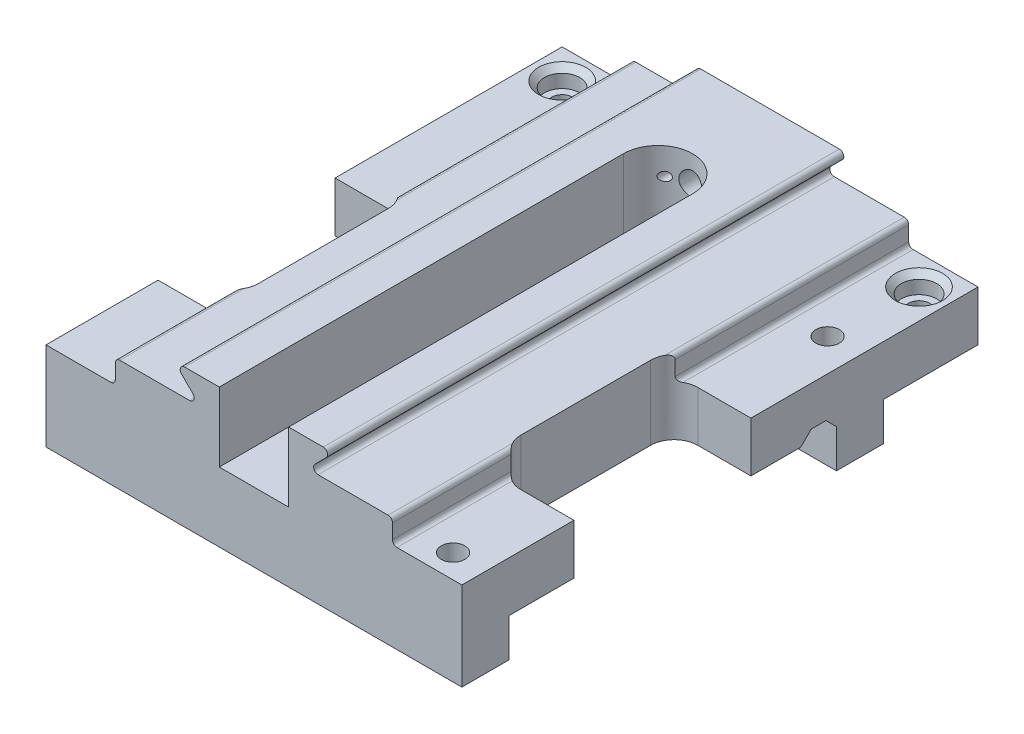
SolidWorks part; units mm, degrees
material "AISI 1020"
ref_plane "Front Plane" through (0, 0, 0) normal (0, 0, 1) x (1, 0, 0)
ref_plane "Top Plane" through (0, 0, 0) normal (0, 1, 0) x (1, 0, 0)
ref_plane "Right Plane" through (0, 0, 0) normal (1, 0, 0) x (0, 0, -1)
sketch "Sketch1" plane through (0, 0, 0) normal (0, 0, 1) x (1, 0, 0)
  line L0 (-70.5, -23.5) -> (-70.5, 23.5) construction
  line L1 (70.5, -23.5) -> (-70.5, -23.5) construction
  line L2 (70.5, -23.5) -> (70.5, 23.5) construction
  line L3 (70.5, 23.5) -> (-70.5, 23.5) construction
  line L4 (-70.5, -23.5) -> (-70.5, 23.5) construction
  line L5 (70.5, -23.5) -> (-70.5, 23.5) construction
  line L6 (70.5, 23.5) -> (-70.5, -23.5) construction
  line L7 (24.5607, 20.9393) -> (20.682, 17.0607)
  line L8 (21.7426, 14.5) -> (45.5, 14.5)
  line L9 (47, 13) -> (47, 8)
  line L10 (48.5, 6.5) -> (70.5, 6.5)
  line L11 (70.5, 6.5) -> (70.5, -23.5)
  line L12 (70.5, -23.5) -> (-70.5, -23.5)
  line L13 (0, -23.5) -> (0, 23.5) construction
  line L14 (-23.5, 23.5) -> (23.5, 23.5)
  line L15 (-70.5, 6.5) -> (-70.5, -23.5)
  line L16 (-48.5, 6.5) -> (-70.5, 6.5)
  line L17 (-47, 13) -> (-47, 8)
  line L18 (-21.7426, 14.5) -> (-45.5, 14.5)
  line L19 (-24.5607, 20.9393) -> (-20.682, 17.0607)
  line L20 (-7, 14.5) -> (7, 14.5) construction
  arc A0 (23.5, 23.5) -> (24.5607, 20.9393) centre (23.5, 22) cw
  arc A1 (20.682, 17.0607) -> (21.7426, 14.5) centre (21.7426, 16) ccw
  arc A2 (45.5, 14.5) -> (47, 13) centre (45.5, 13) cw
  arc A3 (47, 8) -> (48.5, 6.5) centre (48.5, 8) ccw
  arc A4 (-47, 8) -> (-48.5, 6.5) centre (-48.5, 8) cw
  arc A5 (-45.5, 14.5) -> (-47, 13) centre (-45.5, 13) ccw
  arc A6 (-20.682, 17.0607) -> (-21.7426, 14.5) centre (-21.7426, 16) cw
  arc A7 (-23.5, 23.5) -> (-24.5607, 20.9393) centre (-23.5, 22) ccw
  circle A8 centre (0, 14.5) radius 4
  circle A9 centre (7, 14.5) radius 1.5
  circle A10 centre (-7, 14.5) radius 1.5
  point P0 (0, 0)
  point P9 (0, 23.5)
  point P44 (0, 14.5)
  dimension "D10" = 8
  dimension "D12" = 3
  dimension "D3" = 9
  dimension "D4" = 45
  dimension "D7" = 141
  dimension "D8" = 94
  dimension "D9" = 9
  dimension "D11" = 14
  dimension "D5" = 30
extrude "Boss-Extrude1" add sketch "Sketch1" against normal blind 175
sketch "Sketch2" plane through (0, 0, 0) normal (0, 1, 0) x (1, 0, 0)
  line L0 (0, 0) -> (0, 137) construction
  line L1 (-11.75, 0) -> (-11.75, 137)
  line L2 (11.75, 0) -> (11.75, 137)
  line L3 (23.5, 175) -> (-23.5, 175) construction
  line L4 (-70.5, 175) -> (-70.5, 0) construction
  line L5 (-48.5, 175) -> (-70.5, 175) construction
  line L6 (0, 175) -> (0, 0) construction
  arc A0 (-11.75, 0) -> (11.75, 0) centre (0, 0) ccw
  arc A1 (11.75, 137) -> (-11.75, 137) centre (0, 137) ccw
  circle A2 centre (-60.5, 165) radius 6
  circle A3 centre (60.5, 165) radius 6
  point P3 (0, 68.5)
  dimension "D5" = 12
  dimension "D1" = 23.5
  dimension "D2" = 38
  dimension "D3" = 10
  dimension "D4" = 10
extrude "Cut-Extrude1" cut sketch "Sketch2" along normal through all
sketch "Sketch3" plane through (0, 0, 0) normal (0, 1, 0) x (1, 0, 0)
  line L0 (-70.5, 98) -> (-52.5, 98)
  line L1 (-70.5, 175) -> (-70.5, 0) construction
  line L2 (-44.5, 90) -> (-44.5, 46)
  line L3 (-52.5, 38) -> (-70.5, 38)
  line L4 (-70.5, 38) -> (-70.5, 98)
  line L5 (-48.5, 0) -> (-70.5, 0) construction
  line L7 (0, 0) -> (0, 175) construction
  line L8 (23.5, 175) -> (-23.5, 175) construction
  line L9 (11.75, 0) -> (-11.75, 0) construction
  line L10 (70.5, 38) -> (70.5, 98)
  line L11 (52.5, 38) -> (70.5, 38)
  line L12 (44.5, 90) -> (44.5, 46)
  line L13 (70.5, 98) -> (52.5, 98)
  circle A0 centre (-60.5, 165) radius 3.5
  arc A2 (-52.5, 98) -> (-44.5, 90) centre (-52.5, 90) cw
  arc A3 (-44.5, 46) -> (-52.5, 38) centre (-52.5, 46) cw
  circle A4 centre (0, 24) radius 5
  arc A5 (44.5, 46) -> (52.5, 38) centre (52.5, 46) ccw
  arc A6 (52.5, 98) -> (44.5, 90) centre (52.5, 90) ccw
  circle A7 centre (60.5, 165) radius 3.5
  dimension "D4" = 8
  dimension "D7" = 7
  dimension "D9" = 10
  dimension "D1" = 26
  dimension "D2" = 60
  dimension "D3" = 38
  dimension "D8" = 24
extrude "Cut-Extrude2" cut sketch "Sketch3" against normal through all both and the other way through all
sketch "Sketch4" plane through (0, 0, 0) normal (1, 0, 0) x (0, 0, -1)
  line L0 (175, -10.5) -> (143, -10.5)
  line L1 (175, 6.5) -> (175, -23.5) construction
  line L2 (143, -10.5) -> (143, -23.5)
  line L3 (175, -23.5) -> (98, -23.5) construction
  line L4 (143, -23.5) -> (175, -23.5)
  line L5 (175, -23.5) -> (175, -10.5)
  line L6 (127, -23.5) -> (127, -10.5)
  line L7 (127, -10.5) -> (123.4645, -6.9645)
  line L8 (123.4645, -6.9645) -> (118.4645, -6.9645)
  line L9 (118.4645, -6.9645) -> (114.9289, -10.5)
  line L10 (114.9289, -10.5) -> (16, -10.5)
  line L11 (16, -10.5) -> (16, -23.5)
  line L12 (38, -23.5) -> (0, -23.5) construction
  line L13 (16, -23.5) -> (127, -23.5)
  line L18 (0, 6.5) -> (0, -23.5) construction
  dimension "D1" = 16
  dimension "D2" = 16
  dimension "D3" = 32
  dimension "D4" = 135
  dimension "D5" = 13
  dimension "D7" = 5
extrude "Cut-Extrude3" cut sketch "Sketch4" against normal through all both and the other way through all
chamfer "Chamfer1" distance 2 angle 45 3 edges at (0, 0, -19) (-60.5, 6.5, -159) (60.5, 6.5, -159)
sketch "Sketch5" plane through (0, 0, 0) normal (1, 0, 0) x (0, 0, -1)
  line L0 (127, -10.5) -> (123.4645, -6.9645) construction
  line L1 (127, -23.5) -> (127, -10.5) construction
  line L3 (123.4645, -6.9645) -> (118.4645, -6.9645) construction
  line L5 (127, -19.0355) -> (127, -10.5)
  line L6 (127, -10.5) -> (123.4645, -6.9645)
  line L7 (123.4645, -6.9645) -> (118.4645, -6.9645)
  line L8 (118.4645, -6.9645) -> (114.9289, -10.5)
  line L11 (127, -19.0355) -> (118.4645, -19.0355)
  line L12 (118.4645, -19.0355) -> (114.9289, -15.5)
  line L13 (114.9289, -15.5) -> (114.9289, -10.5)
  circle A0 centre (120.9645, -13) radius 3.5
  point P10 (120.9645, -6.9645)
  point P12 (114.9289, -13)
  dimension "D1" = 7
extrude "Boss-Extrude2" add sketch "Sketch5" along normal mid plane 44 contours L13 L12 L11 L5 L6 L7 L8 A0 region at (0, -18.8648, -122.7322)
sketch "Sketch6" plane through (0, 6.5, 0) normal (0, 1, 0) x (1, 0, 0)
  line L0 (59.5, 135) -> (59.5, 8) construction
  line L1 (70.5, 16) -> (70.5, 0) construction
  line L2 (70.5, 143) -> (70.5, 127) construction
  line L4 (70.5, 38) -> (70.5, 0) construction
  circle A0 centre (59.5, 8) radius 4
  circle A1 centre (59.5, 135) radius 4
  circle A2 centre (59.5, 8) radius 2.25
  circle A3 centre (59.5, 135) radius 2.25
  point P7 (70.5, 8)
  point P10 (70.5, 135)
  dimension "D2" = 8
  dimension "D3" = 4.5
  dimension "D1" = 11
extrude "Cut-Extrude4" cut sketch "Sketch6" against normal blind 18
extrude "Cut-Extrude5" cut sketch "Sketch6<2>" against normal through all both and the other way through all contours A2 | A3 region at (59.5, 6.5, -8) region at (59.5, 6.5, -135)
sketch "Sketch6<2>" plane through (0, 6.5, 0) normal (0, 1, 0) x (1, 0, 0) same geometry as "Sketch6"
equation "\"A\"= 141"
equation "\"D7@Sketch1\"=\"A\""
equation "\"D2@Sketch1\"=\"A\"/3"
equation "\"D8@Sketch1\"=\"A\"*2/3"
equation "\"D6@Sketch1\"=\"A\"/3"
equation "\"B\"= 175"
equation "\"D1@Boss-Extrude1\"=\"B\""
equation "\"D1@Sketch2\"=\"A\"/6"
equation "\"C\"= 44"
equation "\"D1@Boss-Extrude2\"=\"C\""
